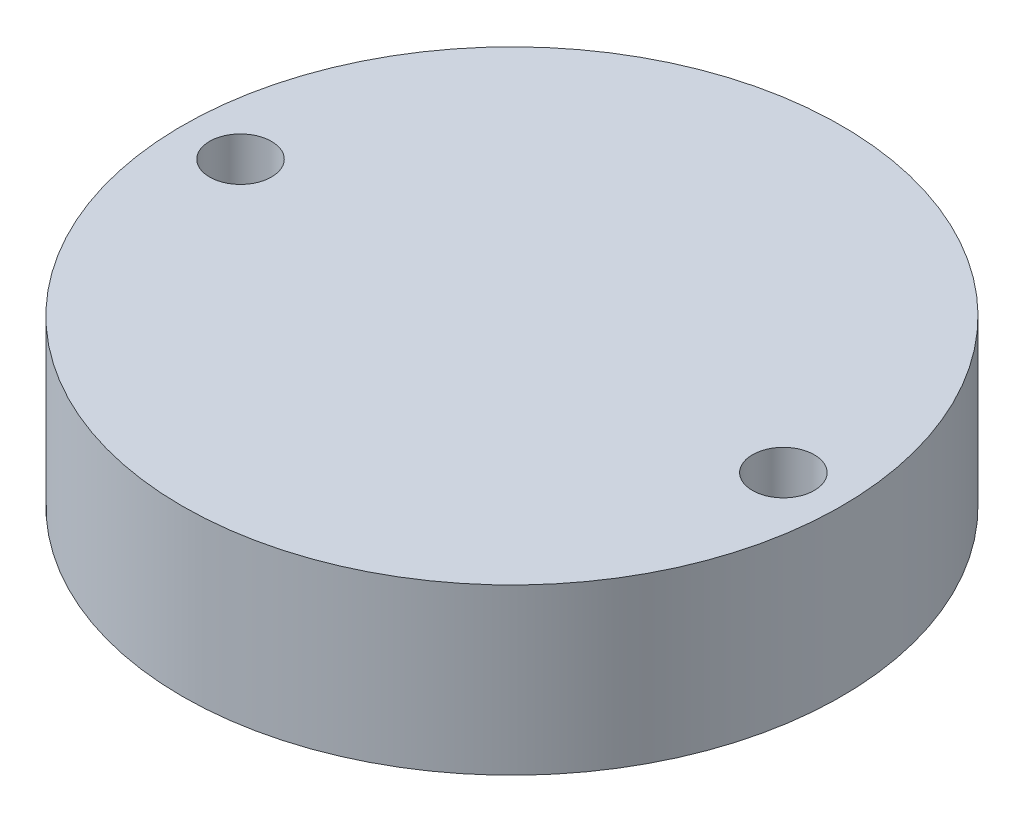
SolidWorks part; units mm, degrees
ref_plane "Front Plane" through (0, 0, 0) normal (0, 0, 1) x (1, 0, 0)
ref_plane "Top Plane" through (0, 0, 0) normal (0, 1, 0) x (1, 0, 0)
ref_plane "Right Plane" through (0, 0, 0) normal (1, 0, 0) x (0, 0, -1)
sketch "Sketch1" plane through (0, 0, 0) normal (0, 1, 0) x (1, 0, 0)
  line L0 (-10.4596, 0) -> (10.4596, 0) construction
  circle A0 centre (0, 0) radius 12.7
  circle A1 centre (0, 0) radius 9.525
  circle A2 centre (-10.4596, 0) radius 1.1931
  circle A3 centre (10.4596, 0) radius 1.1931
  point P4 (-10.3403, 0)
  point P8 (-11.0561, 0)
  point P9 (-10.4596, 0)
  point P11 (0, 0)
  dimension "D1" = 25.4
  dimension "D2" = 19.05
extrude "Boss-Extrude1" add sketch "Sketch1" along normal blind 6.35 contours A0
extrude "Cut-Extrude1" cut sketch "Sketch1<3>" along normal blind 3.175 contours L0 A2 A1 A3 | A2 L0 A3 A1 region at (0, 0, -4.0491) region at (0, 0, 4.0491)
sketch "Sketch1<3>" plane through (0, 0, 0) normal (0, 1, 0) x (1, 0, 0) same geometry as "Sketch1"
extrude "Cut-Extrude2" cut sketch "Sketch1<5>" along direction (0, 1, 0) on the side of the normal through all contours A1 A3 | A3 L0 A1 | L0 A3 A1 | A1 A2 | L0 A1 A2 | A1 L0 A2 region at (-9.4154, 0, -0.2687) region at (-10.521, 0, 0) region at (-9.4154, 0, 0.2687) region at (9.4154, 0, -0.2687) region at (9.4154, 0, 0.2687) region at (10.521, 0, 0)
sketch "Sketch1<5>" plane through (0, 0, 0) normal (0, 1, 0) x (1, 0, 0) same geometry as "Sketch1"
